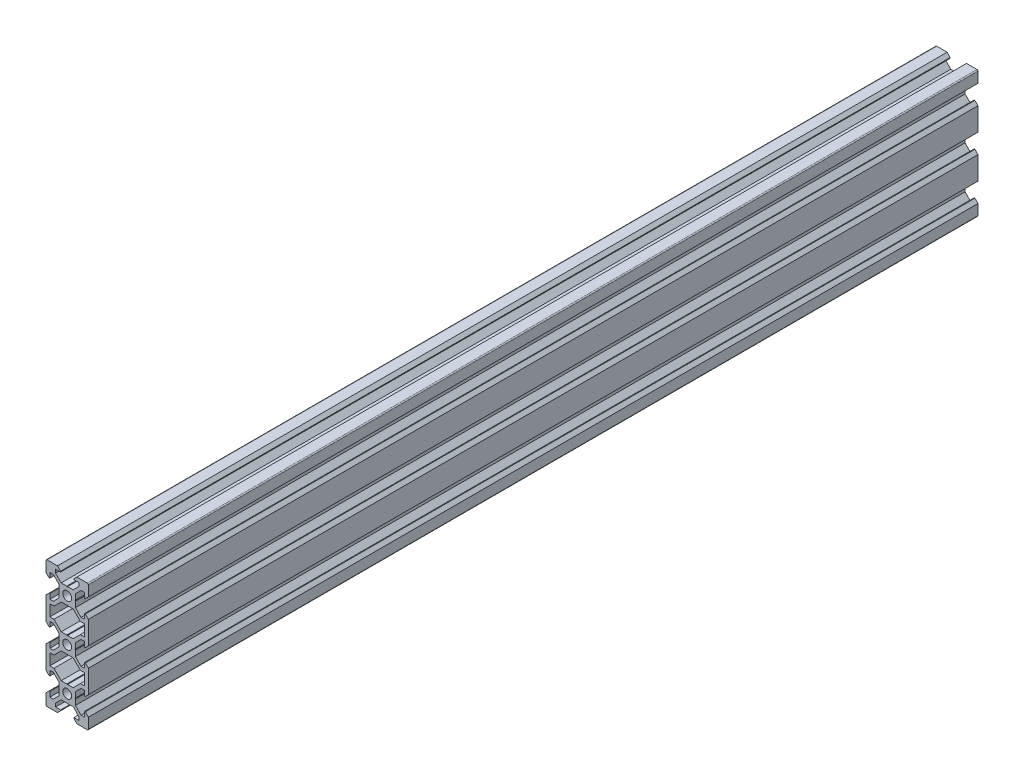
SolidWorks part; units mm, degrees
ref_plane "Plan de face" through (0, 0, 0) normal (0, 0, 1) x (1, 0, 0)
ref_plane "Plan de dessus" through (0, 0, 0) normal (0, 1, 0) x (1, 0, 0)
ref_plane "Plan de droite" through (0, 0, 0) normal (1, 0, 0) x (0, 0, -1)
ref_axis "Axe" through (0, 0, -13.782) along (0, 0, 1)
sketch "Esquisse1" plane through (0, 0, 0) normal (0, 0, 1) x (1, 0, 0)
  line L0 (0, 27.6392) -> (0, -27.6392) construction
  line L1 (-33.6074, 0) -> (33.6074, 0) construction
  line L2 (0, 0) -> (-22.2114, 22.2114) construction
  line L3 (-9.5, 10) -> (-4.58, 10)
  line L4 (-4.58, 10) -> (-3.125, 8.545)
  line L5 (-3.125, 8.545) -> (-3.125, 8.2)
  line L6 (-3.125, 8.2) -> (-5.5, 8.2)
  line L7 (-2.8393, 3.9) -> (-5.5, 6.5607)
  line L8 (-2.8393, 3.9) -> (-0.21, 3.9)
  line L9 (-5.5, 6.5607) -> (-5.5, 8.2)
  line L10 (0, 3.69) -> (0, 2.1)
  line L11 (-3.9, 2.8393) -> (-6.5607, 5.5)
  line L12 (-8.545, 3.125) -> (-8.2, 3.125)
  line L13 (-8.2, 3.125) -> (-8.2, 5.5)
  line L14 (-6.5607, 5.5) -> (-8.2, 5.5)
  line L15 (-10, 4.58) -> (-8.545, 3.125)
  line L16 (-10, 9.5) -> (-10, 4.58)
  line L17 (-0.21, 3.9) -> (0, 3.69)
  line L18 (-3.9, 2.8393) -> (-3.9, 0.21)
  line L19 (-6.2393, -12.7) -> (-8.2, -12.7)
  line L20 (-3.9, 0.21) -> (-3.69, 0)
  line L21 (-0.21, -3.9) -> (0, -3.69)
  line L22 (0, -3.69) -> (0, -2.1)
  line L23 (-6.5607, -5.5) -> (-8.2, -5.5)
  line L24 (-2.8393, -3.9) -> (-0.21, -3.9)
  line L25 (-8.545, -3.125) -> (-8.2, -3.125)
  line L26 (-10, -4.58) -> (-8.545, -3.125)
  line L27 (-8.2, -3.125) -> (-8.2, -5.5)
  line L28 (-2.8393, -3.9) -> (-6.2393, -7.3)
  line L29 (-3.9, -2.8393) -> (-6.5607, -5.5)
  line L30 (-3.9, -2.8393) -> (-3.9, -0.21)
  line L31 (-3.9, -0.21) -> (-3.69, 0)
  line L32 (-6.2393, -7.3) -> (-8.2, -7.3)
  line L33 (-8.2, -7.3) -> (-8.2, -12.7)
  line L34 (-8.2, -10) -> (-10, -10) construction
  line L35 (-10, -15.42) -> (-10, -4.58)
  line L36 (-3.9, -19.79) -> (-3.69, -20)
  line L37 (-3.9, -17.1607) -> (-3.9, -19.79)
  line L38 (-3.9, -17.1607) -> (-6.5607, -14.5)
  line L39 (-2.8393, -16.1) -> (-6.2393, -12.7)
  line L40 (-8.2, -16.875) -> (-8.2, -14.5)
  line L41 (-10, -15.42) -> (-8.545, -16.875)
  line L42 (-8.545, -16.875) -> (-8.2, -16.875)
  line L43 (-2.8393, -16.1) -> (-0.21, -16.1)
  line L44 (-6.5607, -14.5) -> (-8.2, -14.5)
  line L45 (0, -16.31) -> (0, -17.9)
  line L46 (-0.21, -16.1) -> (0, -16.31)
  line L47 (-8.2, -30) -> (-10, -30) construction
  line L48 (-3.69, -20) -> (0, -20) construction
  line L49 (-0.21, -23.9) -> (0, -23.69)
  line L50 (0, -23.69) -> (0, -22.1)
  line L51 (-6.5607, -25.5) -> (-8.2, -25.5)
  line L52 (-2.8393, -23.9) -> (-0.21, -23.9)
  line L53 (-8.545, -23.125) -> (-8.2, -23.125)
  line L54 (-10, -24.58) -> (-8.545, -23.125)
  line L55 (-8.2, -23.125) -> (-8.2, -25.5)
  line L56 (-2.8393, -23.9) -> (-6.2393, -27.3)
  line L57 (-3.9, -22.8393) -> (-6.5607, -25.5)
  line L58 (-3.9, -22.8393) -> (-3.9, -20.21)
  line L59 (-3.9, -20.21) -> (-3.69, -20)
  line L60 (-10, -24.58) -> (-10, -35.42)
  line L61 (-8.2, -32.7) -> (-8.2, -27.3)
  line L62 (-6.2393, -32.7) -> (-8.2, -32.7)
  line L63 (-3.9, -39.79) -> (-3.69, -40)
  line L64 (-3.9, -37.1607) -> (-3.9, -39.79)
  line L65 (-3.9, -37.1607) -> (-6.5607, -34.5)
  line L66 (-2.8393, -36.1) -> (-6.2393, -32.7)
  line L67 (-8.2, -36.875) -> (-8.2, -34.5)
  line L68 (-10, -35.42) -> (-8.545, -36.875)
  line L69 (-8.545, -36.875) -> (-8.2, -36.875)
  line L70 (-2.8393, -36.1) -> (-0.21, -36.1)
  line L71 (-6.5607, -34.5) -> (-8.2, -34.5)
  line L72 (0, -36.31) -> (0, -37.9)
  line L73 (-0.21, -36.1) -> (0, -36.31)
  line L74 (-3.9, -40.21) -> (-3.69, -40)
  line L75 (-6.2393, -27.3) -> (-8.2, -27.3)
  line L76 (-3.9, -42.8393) -> (-3.9, -40.21)
  line L77 (-0.21, -43.9) -> (0, -43.69)
  line L78 (-10, -49.5) -> (-10, -44.58)
  line L79 (-10, -44.58) -> (-8.545, -43.125)
  line L80 (-6.5607, -45.5) -> (-8.2, -45.5)
  line L81 (-8.2, -43.125) -> (-8.2, -45.5)
  line L82 (-8.545, -43.125) -> (-8.2, -43.125)
  line L83 (-3.9, -42.8393) -> (-6.5607, -45.5)
  line L84 (0, -43.69) -> (0, -42.1)
  line L85 (-5.5, -46.5607) -> (-5.5, -48.2)
  line L86 (-2.8393, -43.9) -> (-0.21, -43.9)
  line L87 (-2.8393, -43.9) -> (-5.5, -46.5607)
  line L88 (-3.125, -48.2) -> (-5.5, -48.2)
  line L89 (-3.125, -48.545) -> (-3.125, -48.2)
  line L90 (-4.58, -50) -> (-3.125, -48.545)
  line L91 (-9.5, -50) -> (-4.58, -50)
  arc A0 (0, -2.1) -> (0, 2.1) centre (0, 0) cw
  arc A1 (-9.5, 10) -> (-10, 9.5) centre (-9.5, 9.5) ccw
  arc A2 (0, -37.9) -> (0, -42.1) centre (0, -40) ccw
  arc A3 (-9.5, -50) -> (-10, -49.5) centre (-9.5, -49.5) cw
  arc A4 (0, -17.9) -> (0, -22.1) centre (0, -20) ccw
  point P4 (0, 0)
  point P7 (0, 0)
  point P30 (-10, 10)
  point P60 (0, -20)
  point P111 (-10, -50)
  dimension "D5" = 11
  dimension "D2" = 2.1
  dimension "D3" = 6.25
  dimension "D10" = 0.5
  dimension "D4" = 9.16
  dimension "D6" = 1.5
  dimension "D7" = 1.8
  dimension "D8" = 4.3
  dimension "D9" = 20
  dimension "D11" = 0.42
  dimension "D12" = 10
  dimension "D13" = 1.8
extrude "Boss.-Extru.1" add sketch "Esquisse1" along normal blind 420
sketch "Esquisse3" plane through (0, 0, 420) normal (0, 0, 1) x (1, 0, 0)
  line L0 (0, 0) -> (-9.8536, 9.8536) construction
  line L1 (-8.2, 8.2) -> (-8.2, 6.57)
  line L2 (-8.2, 6.57) -> (-7.54, 6.57)
  line L3 (-7.54, 6.57) -> (-6.57, 7.54)
  line L4 (-8.2, 3.125) -> (-8.2, 5.5) construction
  line L5 (-6.57, 8.2) -> (-6.57, 7.54)
  line L6 (-8.2, 8.2) -> (-6.57, 8.2)
  line L7 (-5.5, 6.5607) -> (-5.5, 8.2) construction
  line L8 (-3.69, -20) -> (0, -20) construction
  line L9 (-8.2, -48.2) -> (-6.57, -48.2)
  line L10 (-6.57, -48.2) -> (-6.57, -47.54)
  line L11 (-7.54, -46.57) -> (-6.57, -47.54)
  line L12 (-8.2, -46.57) -> (-7.54, -46.57)
  line L13 (-8.2, -48.2) -> (-8.2, -46.57)
  arc A0 (-9.5, 10) -> (-10, 9.5) centre (-9.5, 9.5) ccw construction
  point P13 (-7.055, 7.055)
  point P14 (-6.57, 7.87)
  point P26 (-7.055, -47.055)
  dimension "D1" = 1.07
extrude "Enlèv. mat.-Extru.1" [suppressed] cut sketch "Esquisse3" against normal through all
mirror "Symétrie1" about plane through (0, 3.69, 420) normal (-1, 0, 0) of "Enlèv. mat.-Extru.1", "Boss.-Extru.1"
